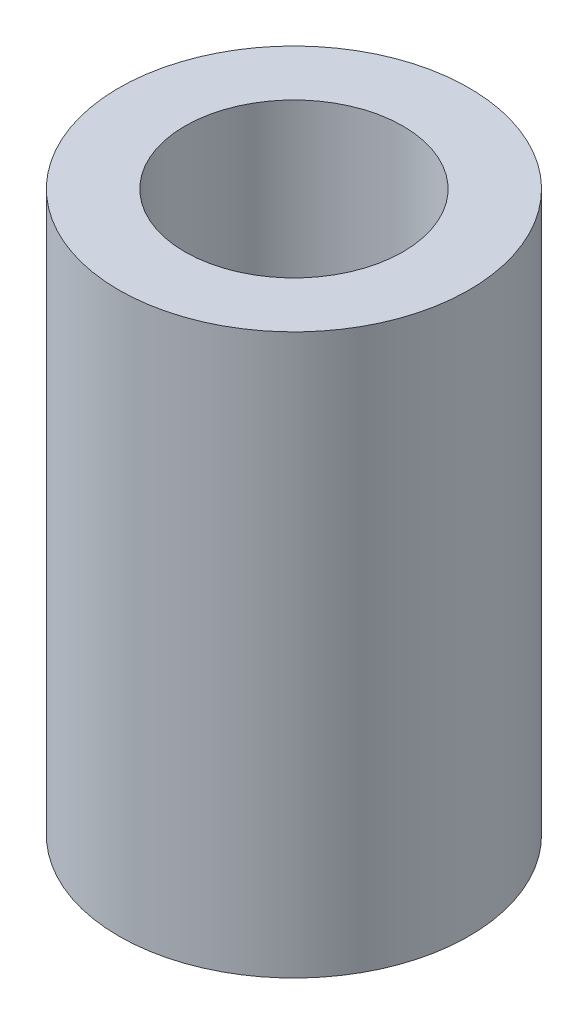
SolidWorks part; units mm, degrees
ref_plane "Front Plane" through (0, 0, 0) normal (0, 0, 1) x (1, 0, 0)
ref_plane "Top Plane" through (0, 0, 0) normal (0, 1, 0) x (1, 0, 0)
ref_plane "Right Plane" through (0, 0, 0) normal (1, 0, 0) x (0, 0, -1)
sketch "Sketch1" plane through (0, 0, 0) normal (0, 1, 0) x (1, 0, 0)
  circle A0 centre (0, 0) radius 10
  dimension "SLEEVE_OD" = 20
extrude "Boss-Extrude1" add sketch "Sketch1" along normal blind 31.9621
sketch "Sketch2" plane through (0, 0, 0) normal (0, 1, 0) x (1, 0, 0)
  circle A0 centre (0, 0) radius 6.227
  dimension "BORE_D" = 12.454
extrude "Cut-Extrude1" cut sketch "Sketch2" along normal through all
chamfer "Chamfer1" distance 1.6497 angle 60 rebuild error yes
